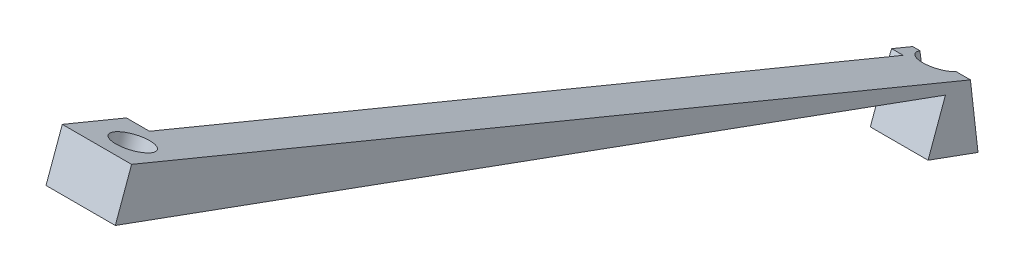
SolidWorks part; units mm, degrees
ref_plane "Front Plane" through (0, 0, 0) normal (0, 0, 1) x (1, 0, 0)
ref_plane "Top Plane" through (0, 0, 0) normal (0, 1, 0) x (1, 0, 0)
ref_plane "Right Plane" through (0, 0, 0) normal (1, 0, 0) x (0, 0, -1)
sketch "Sketch1" plane through (0, 0, 0) normal (1, 0, 0) x (0, 0, -1)
  line L0 (-74.6958, 27.9916) -> (-71.873, 35.7473)
  line L1 (-71.873, 35.7473) -> (73.385, -24.2081)
  line L2 (-74.6958, 27.9916) -> (69.0604, -24.3314)
  line L3 (69.0604, -24.3314) -> (66.0507, -32.6007)
  line L4 (66.0507, -32.6007) -> (74.6958, -35.7473)
  line L5 (74.6958, -35.7473) -> (73.385, -24.2081)
extrude "Boss-Extrude1" add sketch "Sketch1" along normal blind 8
sketch "Sketch2" plane through (0, 0, 0) normal (-1, 0, 0) x (0, 0, 1)
  line L0 (74.6958, 27.9916) -> (63.4195, 23.8873)
  line L1 (74.6958, 27.9916) -> (-69.0604, -24.3314) construction
  line L2 (74.6958, 27.9916) -> (71.873, 35.7473)
  line L3 (63.4195, 23.8873) -> (60.7707, 31.1648)
  line L4 (-73.385, -24.2081) -> (71.873, 35.7473) construction
  line L5 (60.7707, 31.1648) -> (71.873, 35.7473)
extrude "Boss-Extrude2" add sketch "Sketch2" along normal blind 4
sketch "Sketch6" plane through (0, 0, 0) normal (-1, 0, 0) x (0, 0, 1)
  line L0 (-74.6958, -35.7473) -> (-66.0507, -32.6007)
  line L1 (-66.0507, -32.6007) -> (-69.0604, -24.3314)
  line L3 (-74.6958, -35.7473) -> (-73.385, -24.2081) construction
  line L4 (-73.5861, -25.9786) -> (-74.6958, -35.7473)
  line L5 (-69.0604, -24.3314) -> (-69.7334, -22.701)
  line L6 (-73.385, -24.2081) -> (60.7707, 31.1648) construction
  line L7 (-69.7334, -22.701) -> (-73.385, -24.2081)
  line L8 (-73.385, -24.2081) -> (-73.5861, -25.9786)
extrude "Boss-Extrude3" add sketch "Sketch6" along normal blind 2
sketch "Sketch4" plane through (0, 0.7104, -0.2586) normal (0, -0.9397, 0.342) x (-1, 0, 0)
  line L0 (-2.3942, -73.9951) -> (-2.3942, -73.4853) construction
  line L1 (-8, -79.7648) -> (-8, -70.1034) construction
  line L2 (-8, -79.7648) -> (1.7822, -79.7648) construction
  line L3 (1.7822, -79.7648) -> (1.7822, -70.1034) construction
  line L4 (-8, -70.1034) -> (1.7822, -70.1034) construction
  line L5 (-2.3942, -73.9951) -> (-2.3942, 77.0049) construction
  circle A0 centre (-2.3942, -73.4853) radius 1.6
  circle A1 centre (-2.3942, 77.0049) radius 1.6
extrude "Cut-Extrude1" cut sketch "Sketch4" against normal through all and the other way blind 12
ref_plane "Plane1" through (0, 5.4089, -1.9687) normal (0, -0.9397, 0.342) x (-1, 0, 0)
sketch "Sketch5" plane through (0, 5.4089, -1.9687) normal (0, -0.9397, 0.342) x (-1, 0, 0)
  line L0 (-2.3942, -73.4853) -> (-2.3942, 77.5147) construction
  circle A0 centre (-2.3942, -73.4853) radius 3.1499
  circle A1 centre (-2.3942, 77.5147) radius 3.1499
extrude "Cut-Extrude2" cut sketch "Sketch5" against normal blind 10
extrude "Cut-Extrude3" cut sketch "Sketch5<2>" along normal blind 9
sketch "Sketch5<2>" plane through (0, 5.4089, -1.9687) normal (0, -0.9397, 0.342) x (-1, 0, 0) same geometry as "Sketch5"
